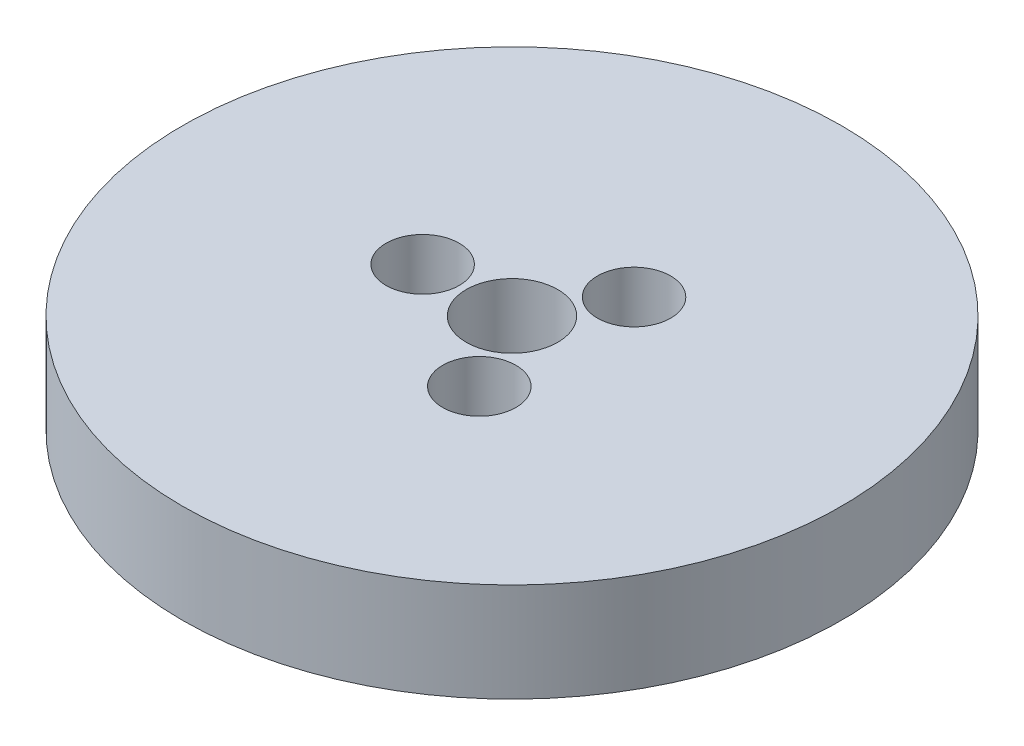
SolidWorks part; units mm, degrees
ref_plane "Front Plane" through (0, 0, 0) normal (0, 0, 1) x (1, 0, 0)
ref_plane "Top Plane" through (0, 0, 0) normal (0, 1, 0) x (1, 0, 0)
ref_plane "Right Plane" through (0, 0, 0) normal (1, 0, 0) x (0, 0, -1)
sketch "Sketch1" plane through (0, 0, 0) normal (0, 1, 0) x (1, 0, 0)
  circle A0 centre (0, 0) radius 90
  dimension "FLANGE_OD" = 180
extrude "Boss-Extrude1" add sketch "Sketch1" along normal blind 27
sketch "Sketch2" plane through (0, 0, 0) normal (0, 1, 0) x (1, 0, 0)
  circle A0 centre (0, 0) radius 12.5
  dimension "BORE_D" = 25
extrude "Cut-Extrude1" cut sketch "Sketch2" along normal through all
sketch "Sketch3" plane through (0, 27, 0) normal (0, 1, 0) x (1, 0, 0)
  circle A0 centre (0, 0) radius 24.4003 construction
  circle A1 centre (-24.4003, 0) radius 10
  dimension "BOLT_D" = 20
  dimension "BOLT_PCD" = 48.8007
extrude "Cut-Extrude2" cut sketch "Sketch3" against normal blind 24.7382
pattern_circular "CirPattern1" count 3 over 360 about axis through (0, 0, 0) along (0, 1, 0) of "Cut-Extrude2"
